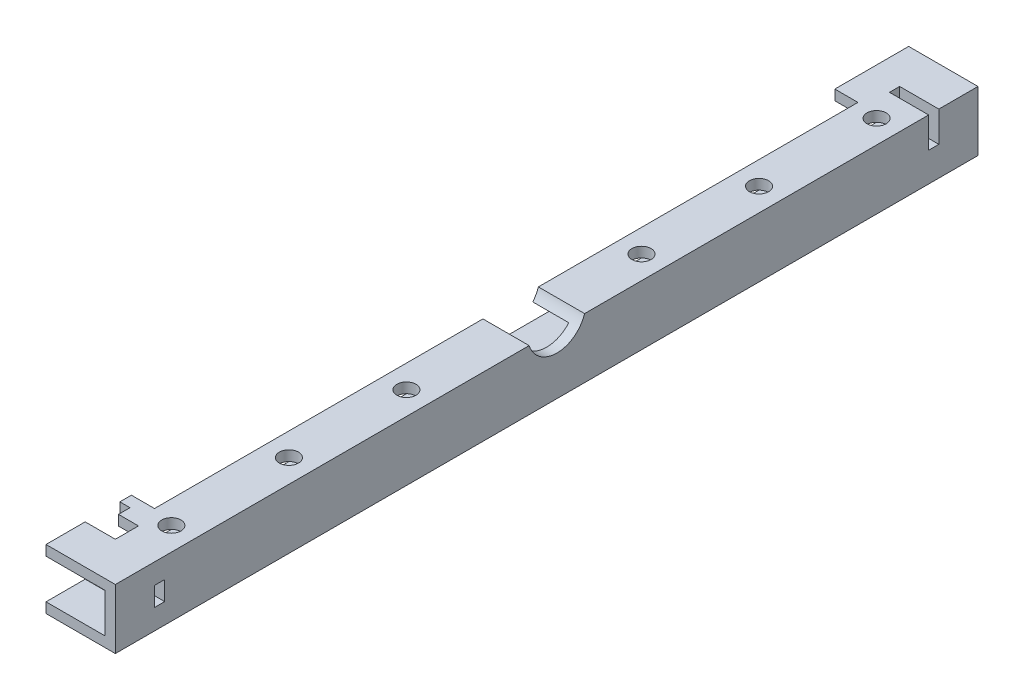
SolidWorks part; units mm, degrees
ref_plane "Front" through (0, 0, 0) normal (0, 0, 1) x (1, 0, 0)
ref_plane "Top" through (0, 0, 0) normal (0, 1, 0) x (1, 0, 0)
ref_plane "Right" through (0, 0, 0) normal (1, 0, 0) x (0, 0, -1)
sketch "Sketch1" plane through (0, 0, 0) normal (0, 0, 1) x (1, 0, 0)
  line L0 (0, 0) -> (11.24, 0)
  line L1 (11.24, 0) -> (11.24, 9.7)
  line L2 (11.24, 9.7) -> (0, 9.7)
  line L3 (0, 1.65) -> (0, 0)
  line L4 (0, 1.65) -> (9.59, 1.65)
  line L6 (9.59, 1.65) -> (9.59, 8.05)
  line L7 (9.59, 8.05) -> (0, 8.05)
  line L8 (0, 9.7) -> (0, 8.05)
extrude "Extrude4" add sketch "Sketch1" along normal blind 139.83
sketch "Sketch2" plane through (0, 9.7, 0) normal (0, 1, 0) x (-1, 0, 0)
  line L5 (-11.24, 6.35) -> (-4.89, 6.35)
  line L6 (-11.24, 139.83) -> (-11.24, 0) construction
  line L7 (-4.89, 6.35) -> (-4.89, 8)
  line L8 (-4.89, 8) -> (-11.24, 8)
  line L9 (-11.24, 8) -> (-11.24, 6.35)
extrude "Cut-Extrude2" cut sketch "Sketch2" against normal blind 4.95
sketch "Sketch4" plane through (0, 9.7, 0) normal (0, 1, 0) x (-1, 0, 0)
  line L0 (0, 11.97) -> (-3.75, 11.97)
  line L1 (0, 139.83) -> (0, 0) construction
  line L2 (-3.75, 125.99) -> (0, 125.99)
  line L3 (-3.75, 125.99) -> (-3.75, 11.97)
  line L4 (0, 125.99) -> (0, 11.97)
  line L5 (0, 133.48) -> (-4.89, 133.48)
  line L6 (-4.89, 133.48) -> (-4.89, 129.73)
  line L7 (-4.89, 129.73) -> (-1.65, 129.73)
  line L8 (-1.65, 129.73) -> (-1.65, 127.86)
  line L9 (-1.65, 127.86) -> (0, 127.86)
  line L10 (0, 127.86) -> (0, 133.48)
  line L11 (-11.24, 139.83) -> (-11.24, 8) construction
  circle A0 centre (-7.495, 127) radius 1.55
  circle A1 centre (-7.495, 12.7) radius 1.55
  circle A2 centre (-7.495, 88.9) radius 1.55
  circle A3 centre (-7.495, 107.95) radius 1.55
  circle A4 centre (-7.495, 50.8) radius 1.55
  circle A5 centre (-7.495, 31.75) radius 1.55
  dimension "D1" = 3.745
extrude "Cut-Extrude3" cut sketch "Sketch4" against normal blind 1.65
sketch "Sketch5" plane through (0, 0, 0) normal (0, -1, 0) x (1, 0, 0)
  line L0 (0, 133.475) -> (4.92, 133.475)
  line L1 (0, 139.83) -> (0, 0) construction
  line L2 (4.92, 133.475) -> (4.92, 129.725)
  line L3 (4.92, 129.725) -> (2.04, 129.725)
  line L4 (2.04, 129.725) -> (2.04, 127.855)
  line L5 (2.04, 127.855) -> (0, 127.855)
  line L6 (0, 127.855) -> (0, 133.475)
  line L7 (0, 6.35) -> (4.95, 6.35)
  line L8 (4.95, 6.35) -> (4.95, 8)
  line L9 (4.95, 8) -> (3.3, 8)
  line L10 (3.3, 8) -> (3.3, 11.24)
  line L11 (3.3, 11.24) -> (1.65, 11.24)
  line L12 (1.65, 11.24) -> (1.65, 8)
  line L13 (1.65, 8) -> (0, 8)
  line L14 (0, 8) -> (0, 6.35)
extrude "Cut-Extrude4" cut sketch "Sketch5" against normal blind 1.65
sketch "Sketch6" plane through (11.24, 0, 0) normal (1, 0, 0) x (0, 0, -1)
  line L1 (-133.48, 6.4) -> (-131.83, 6.4)
  line L2 (-133.48, 6.4) -> (-133.48, 3.3)
  line L3 (-133.48, 3.3) -> (-131.83, 3.3)
  line L4 (-131.83, 6.4) -> (-131.83, 3.3)
extrude "Cut-Extrude5" cut sketch "Sketch6" against normal blind 1.65
sketch "Sketch7" plane through (11.24, 0, 0) normal (1, 0, 0) x (0, 0, -1)
  circle A0 centre (-68.2625, 11.1125) radius 4.71
extrude "Cut-Extrude6" cut sketch "Sketch7" against normal through all
